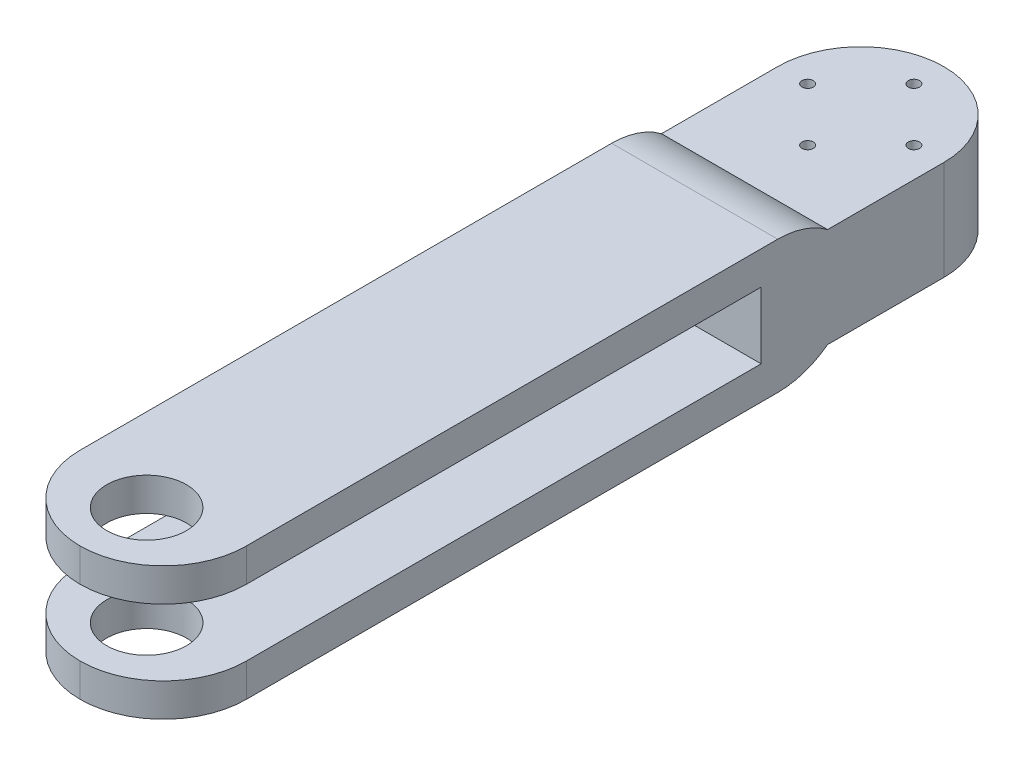
SolidWorks part; units mm, degrees
ref_plane "Plan de face" through (0, 0, 0) normal (0, 0, 1) x (1, 0, 0)
ref_plane "Plan de dessus" through (0, 0, 0) normal (0, 1, 0) x (1, 0, 0)
ref_plane "Plan de droite" through (0, 0, 0) normal (1, 0, 0) x (0, 0, -1)
sketch "Esquisse1" plane through (0, 0, 0) normal (1, 0, 0) x (0, 0, -1)
  line L0 (90, 10) -> (-10, 10)
  line L1 (-10, 10) -> (-10, 5)
  line L2 (90, 10) -> (90, 7.5)
  line L3 (90, 7.5) -> (120, 7.5)
  line L4 (-10, 5) -> (80, 5)
  line L5 (80, 5) -> (80, -5)
  line L6 (120, 7.5) -> (120, -7.5)
  line L7 (55, 0) -> (-55, 0) construction
  line L8 (-10, -5) -> (80, -5)
  line L9 (90, -7.5) -> (120, -7.5)
  line L10 (90, -10) -> (90, -7.5)
  line L11 (-10, -10) -> (-10, -5)
  line L12 (90, -10) -> (-10, -10)
  point P2 (0, 0)
  point P12 (120, 0)
  point P13 (80, 0)
  dimension "D1" = 130
  dimension "10" = 10
  dimension "D2" = 15
  dimension "D3" = 5
  dimension "D4" = 10
  dimension "D5" = 10
  dimension "D6" = 80
extrude "Boss.-Extru.1" add sketch "Esquisse1" along normal mid plane 25
fillet "Congé1" radius 12.5 8 edges at (0, -10, -90) (0, 10, -90) (-12.5, -7.5, 10) (-12.5, 7.5, 10) (12.5, -7.5, 10) (12.5, 7.5, 10) (-12.5, 0, -120) (12.5, 0, -120)
sketch "Esquisse2" plane through (0, 7.5, 0) normal (0, 1, 0) x (1, 0, 0)
  line L0 (-12.5, 107.5) -> (12.5, 107.5) construction
  line L1 (0, 120) -> (0, 226.6844) construction
  arc A0 (0, 120) -> (-12.5, 107.5) centre (0, 107.5) ccw construction
  circle A1 centre (8, 107.5) radius 0.85
  circle A2 centre (0, 115.5) radius 0.85
  circle A3 centre (-8, 107.5) radius 0.85
  circle A4 centre (0, 99.5) radius 0.85
  point P12 (0, 173.3422)
  dimension "D1" = 1.7
  dimension "D2" = 1.7
  dimension "D3" = 8
  dimension "D4" = 8
extrude "Enlèv. mat.-Extru.1" cut sketch "Esquisse2" against normal through all
sketch "Esquisse3" plane through (0, 10, 0) normal (0, 1, 0) x (1, 0, 0)
  circle A0 centre (0, 0) radius 6
  dimension "D1" = 12
extrude "Enlèv. mat.-Extru.2" cut sketch "Esquisse3" against normal through all
